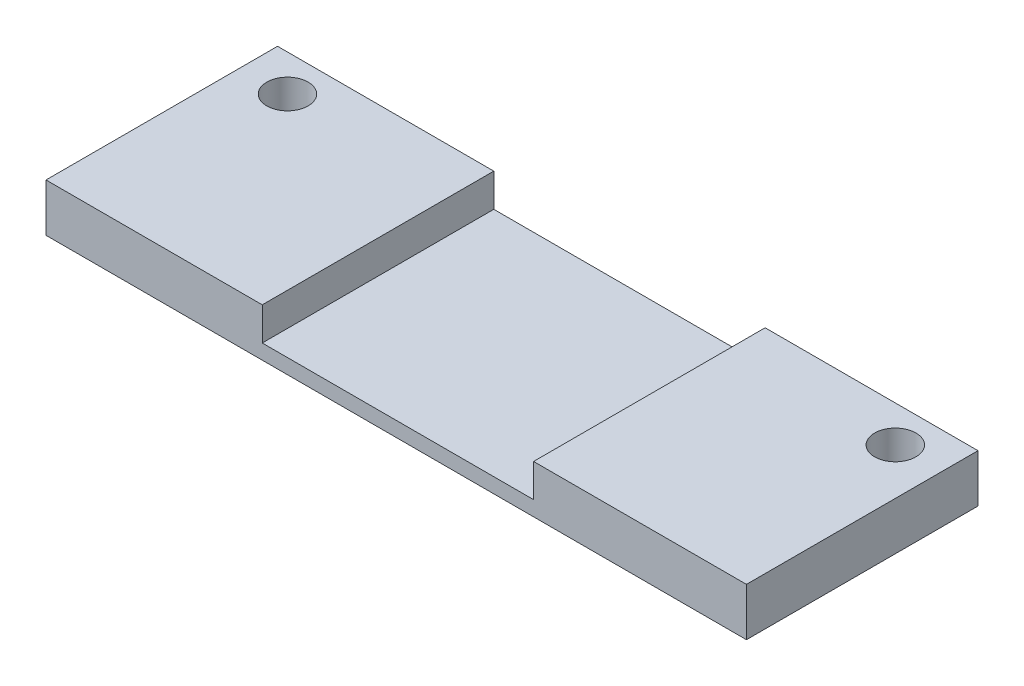
SolidWorks part; units mm, degrees
ref_plane "前视基准面" through (0, 0, 0) normal (0, 0, 1) x (1, 0, 0)
ref_plane "上视基准面" through (0, 0, 0) normal (0, 1, 0) x (1, 0, 0)
ref_plane "右视基准面" through (0, 0, 0) normal (1, 0, 0) x (0, 0, -1)
other "Configuration Table"
sketch "草图1" plane through (0, 0, 0) normal (0, 1, 0) x (1, 0, 0)
  line L0 (6.6691, 5.4506) -> (-1.4309, 5.4506)
  line L1 (-14.5059, 5.4506) -> (27.8441, 5.4506)
  line L2 (-14.5059, 5.4506) -> (-14.5059, -8.5494)
  line L3 (-14.5059, -8.5494) -> (27.8441, -8.5494)
  line L4 (27.8441, 5.4506) -> (27.8441, -8.5494)
  line L5 (6.6691, 5.4506) -> (14.7691, 5.4506)
  line L7 (-1.4309, 5.4506) -> (14.7691, 5.4506)
  line L11 (-1.4309, 5.4506) -> (14.973, 5.4506)
  line L12 (-1.4309, 5.4506) -> (-1.4309, -8.5494)
  line L13 (-1.4309, -8.5494) -> (14.973, -8.5494)
  line L14 (14.973, 5.4506) -> (14.973, -8.5494)
  circle A0 centre (-11.7059, 3.2506) radius 1.25
  circle A1 centre (25.0441, 3.2506) radius 1.25
  dimension "D3" = 2.5
  dimension "D10" = 2.5
  dimension "D1" = 42.35
  dimension "D2" = 14
  dimension "D4" = 2.8
  dimension "D5" = 2.2
  dimension "D6" = 2.8
  dimension "D7" = 2.2
  dimension "D8" = 8.1
  dimension "D9" = 8.1
extrude "凸台-拉伸2" add sketch "草图1" along normal blind 2.9 contours L12 L1 L2 L3 A0 | L1 L14 L3 L4 A1 region at (-7.8654, 0, 1.6816) region at (21.3067, 0, 1.6838)
extrude "凸台-拉伸3" add sketch "草图1<4>" along normal blind 0.9 contours L14 L1 L0 L12 L3 region at (6.771, 0, 1.5494)
sketch "草图1<4>" plane through (0, 0, 0) normal (0, 1, 0) x (1, 0, 0) same geometry as "草图1"
